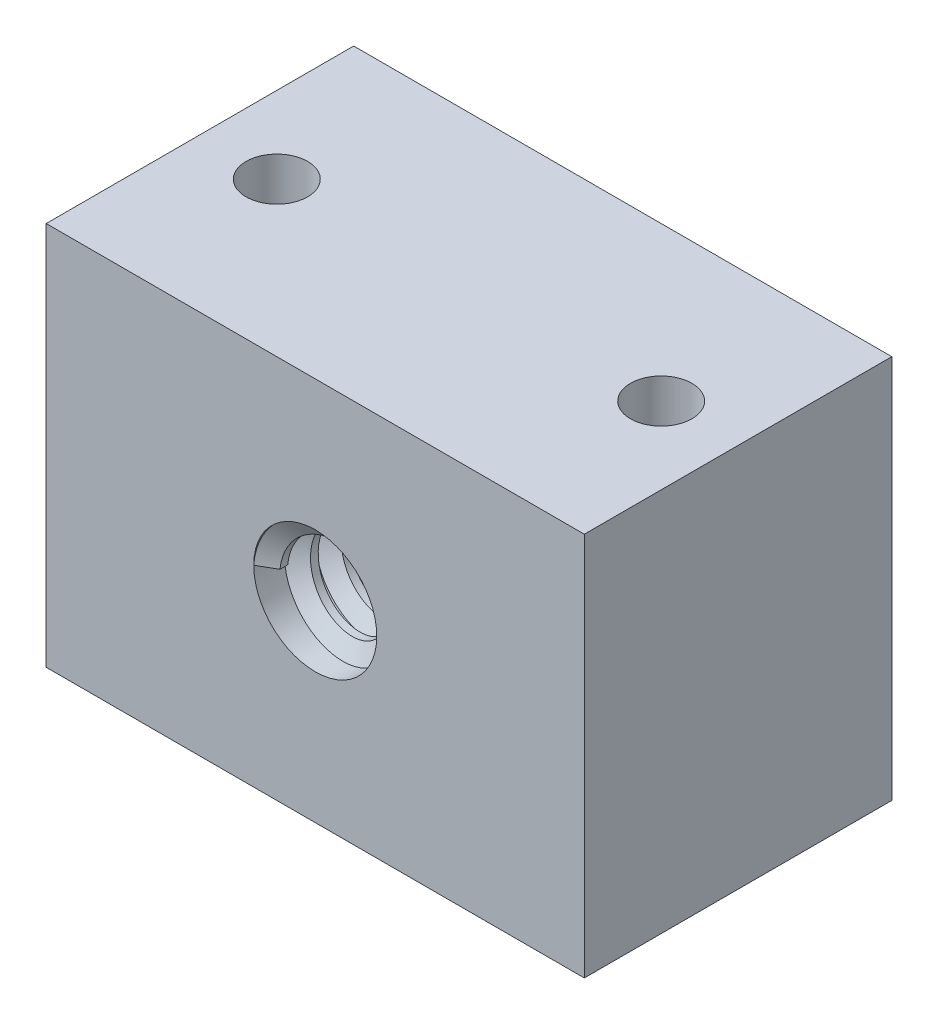
SolidWorks part; units mm, degrees
ref_plane "Front Plane" through (0, 0, 0) normal (0, 0, 1) x (1, 0, 0)
ref_plane "Top Plane" through (0, 0, 0) normal (0, 1, 0) x (1, 0, 0)
ref_plane "Right Plane" through (0, 0, 0) normal (1, 0, 0) x (0, 0, -1)
sketch "Sketch1" plane through (0, 0, 0) normal (0, 0, 1) x (1, 0, 0)
  line L1 (-17.5, -12.5) -> (17.5, -12.5)
  line L2 (-17.5, -12.5) -> (-17.5, 12.5)
  line L3 (-17.5, 12.5) -> (17.5, 12.5)
  line L4 (17.5, -12.5) -> (17.5, 12.5)
  line L5 (-17.5, -12.5) -> (17.5, 12.5) construction
  line L6 (-17.5, 12.5) -> (17.5, -12.5) construction
  point P0 (0, 0)
  dimension "D1" = 35
  dimension "D2" = 25
extrude "Boss-Extrude1" add sketch "Sketch1" along normal blind 20
sketch "Sketch2" plane through (0, 0, 20) normal (0, 0, 1) x (1, 0, 0)
  circle A0 centre (0, 0) radius 4
  dimension "D1" = 8
extrude "Cut-Extrude1" cut sketch "Sketch2" against normal through all
sketch "Sketch3" plane through (0, 12.5, 0) normal (0, 1, 0) x (1, 0, 0)
  line L0 (0, 0) -> (0, -21.5368) construction
  line L1 (17.5, -10) -> (-17.5, -10) construction
  line L2 (17.5, -20) -> (17.5, 0) construction
  line L3 (-17.5, -20) -> (-17.5, 0) construction
  circle A0 centre (12.5, -10) radius 2
  circle A1 centre (-12.5, -10) radius 2
  dimension "D1" = 4
  dimension "D2" = 12.5
extrude "Cut-Extrude2" cut sketch "Sketch3" against normal through all contours A1 | A0
thread "Thread1" pitch 2 method extrude profile "Thread Profile1" start angle 0, offset 0, length 18, pitch 2, diameter 8
ref_plane "Plane1" through (-4, 0, 20) normal (0, -1, 0) x (-1, 0, 0)
sketch "Thread Profile1" plane through (-4, 0, 20) normal (0, -1, 0) x (-1, 0, 0)
  line L0 (0, 0) -> (0, 2) construction
  line L11 (0, 0) -> (0, 1.75)
  line L12 (0, 1.75) -> (-1.0825, 1.125)
  line L13 (-1.0825, 1.125) -> (-1.0825, 0.625)
  line L15 (-1.0825, 0.625) -> (0, 0)
  line L17 (-1.0825, 0.875) -> (0, 0.875) construction
  point P2 (0, 0)
  dimension "Pitch" = 2
  dimension "Profile_Angle" = 60
  dimension "Profile_Land" = 0.5
  dimension "Profile_Height" = 1.0825
